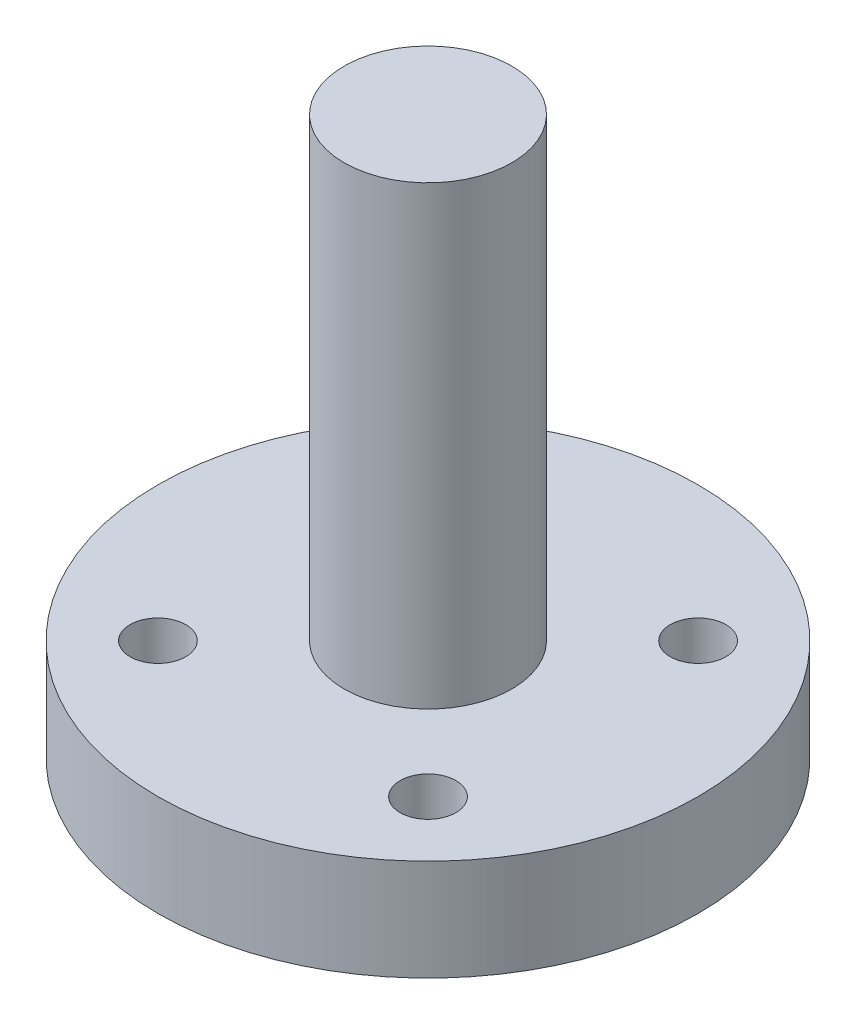
SolidWorks part; units mm, degrees
material "6061 Alloy"
ref_plane "Front Plane" through (0, 0, 0) normal (0, 0, 1) x (1, 0, 0)
ref_plane "Top Plane" through (0, 0, 0) normal (0, 1, 0) x (1, 0, 0)
ref_plane "Right Plane" through (0, 0, 0) normal (1, 0, 0) x (0, 0, -1)
sketch "Sketch1" plane through (0, 0, 0) normal (0, 1, 0) x (1, 0, 0)
  circle A0 centre (0, 0) radius 16
  dimension "D1" = 32
extrude "Boss-Extrude1" add sketch "Sketch1" along normal blind 6
sketch "Sketch3" plane through (0, 6, 0) normal (0, 1, 0) x (1, 0, 0)
  circle A1 centre (0, 0) radius 4.965
  dimension "D2" = 9.93
sketch "Sketch4" plane through (0, 0, 0) normal (0, -1, 0) x (1, 0, 0)
  line L1 (8, 8) -> (-8, 8) construction
  line L2 (8, 8) -> (8, -8) construction
  line L3 (8, -8) -> (-8, -8) construction
  line L4 (-8, 8) -> (-8, -8) construction
  line L5 (8, 8) -> (-8, -8) construction
  line L6 (8, -8) -> (-8, 8) construction
  point P0 (0, 0)
  dimension "D1" = 16
  dimension "D2" = 90
hole_wizard "Tap Drill for M4x0.7 Tap1" positions "Sketch5" profile "Sketch6" hole size "M4x0.7" standard "ANSI Metric" end condition through all
sketch "Sketch5" plane through (0, 0, 0) normal (0, -1, 0) x (-1, 0, 0)
  point P0 (-8, 8)
  point P3 (-8, -8)
  point P6 (8, -8)
  point P9 (8, 8)
sketch "Sketch6" plane through (8, 0, -8) normal (1, 0, 0) x (0, 0, -1)
  line L0 (0, 0) -> (0, 6)
  line L1 (0, 6) -> (1.65, 6)
  line L2 (1.65, 6) -> (1.65, 0)
  line L5 (1.65, 0) -> (0, 0)
  line L11 (0, -6.35) -> (0, 107.95) construction
  dimension "Thru Hole Dia." = 3.3
  dimension "Thru Hole Depth" = 6
extrude "Boss-Extrude2" add sketch "Sketch3" along normal blind 27
